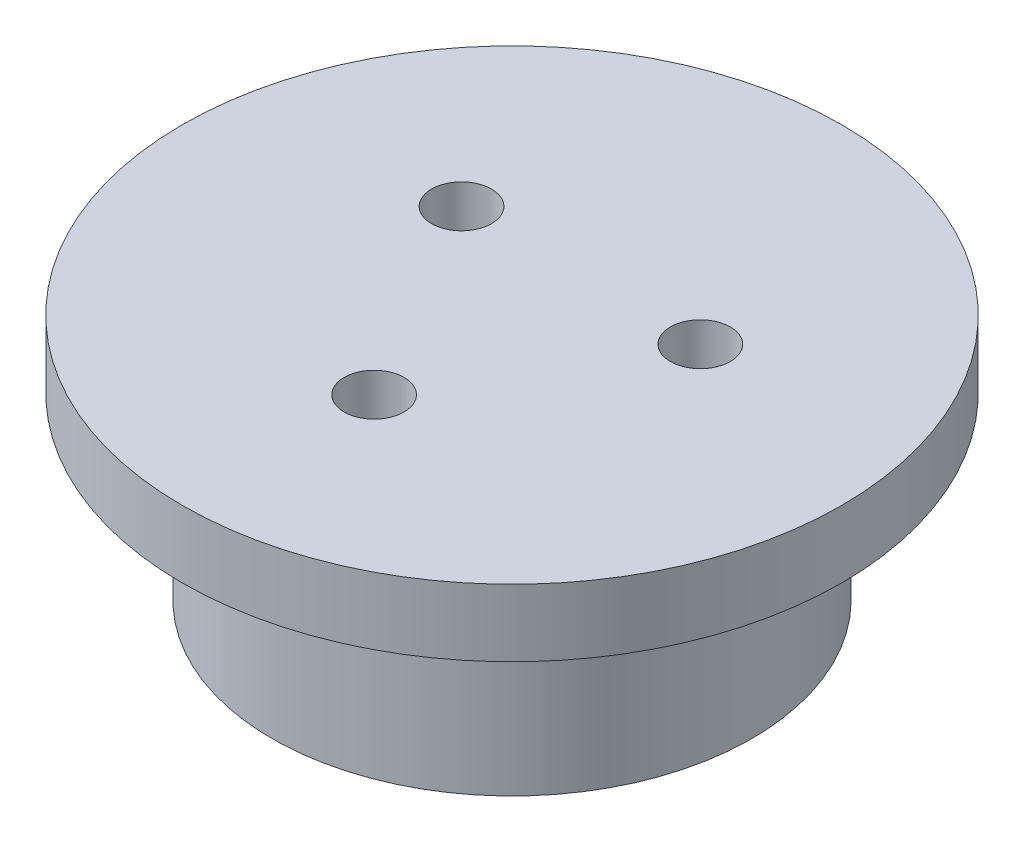
SolidWorks part; units mm, degrees
material "1060 Alloy"
ref_plane "Front Plane" through (0, 0, 0) normal (0, 0, 1) x (1, 0, 0)
ref_plane "Top Plane" through (0, 0, 0) normal (0, 1, 0) x (1, 0, 0)
ref_plane "Right Plane" through (0, 0, 0) normal (1, 0, 0) x (0, 0, -1)
sketch "Sketch1" plane through (0, 0, 0) normal (0, 1, 0) x (1, 0, 0)
  line L0 (0, 0) -> (0, 27.5) construction
  line L1 (0, 0) -> (9.9593, 5.75) construction
  line L2 (0, 0) -> (0, -11.5) construction
  line L3 (0, 0) -> (-9.9593, 5.75) construction
  circle A0 centre (0, 0) radius 27.5
  circle A1 centre (-9.9593, 5.75) radius 2.5
  circle A2 centre (9.9593, 5.75) radius 2.5
  circle A3 centre (0, -11.5) radius 2.5
  dimension "D3" = 5
  dimension "D4" = 55
  dimension "D1" = 120
  dimension "D2" = 120
  dimension "D5" = 11.5
extrude "Boss-Extrude1" add sketch "Sketch1" along normal blind 5.6
sketch "Sketch2" plane through (0, 0, 0) normal (0, -1, 0) x (1, 0, 0)
  circle A0 centre (0, 0) radius 20
  circle A1 centre (0, 11.5) radius 2.5
  circle A2 centre (9.9593, -5.75) radius 2.5
  circle A3 centre (-9.9593, -5.75) radius 2.5
  circle A4 centre (0, 11.5) radius 2.5 construction
  circle A5 centre (-9.9593, -5.75) radius 2.5 construction
  circle A6 centre (9.9593, -5.75) radius 2.5 construction
  dimension "D1" = 40
extrude "Boss-Extrude2" add sketch "Sketch2" along normal blind 15
sketch "Sketch3" plane through (0, -15, 0) normal (0, -1, 0) x (1, 0, 0)
  circle A0 centre (0, 0) radius 17.5
  dimension "D1" = 35
extrude "Cut-Extrude1" cut sketch "Sketch3" against normal blind 5
